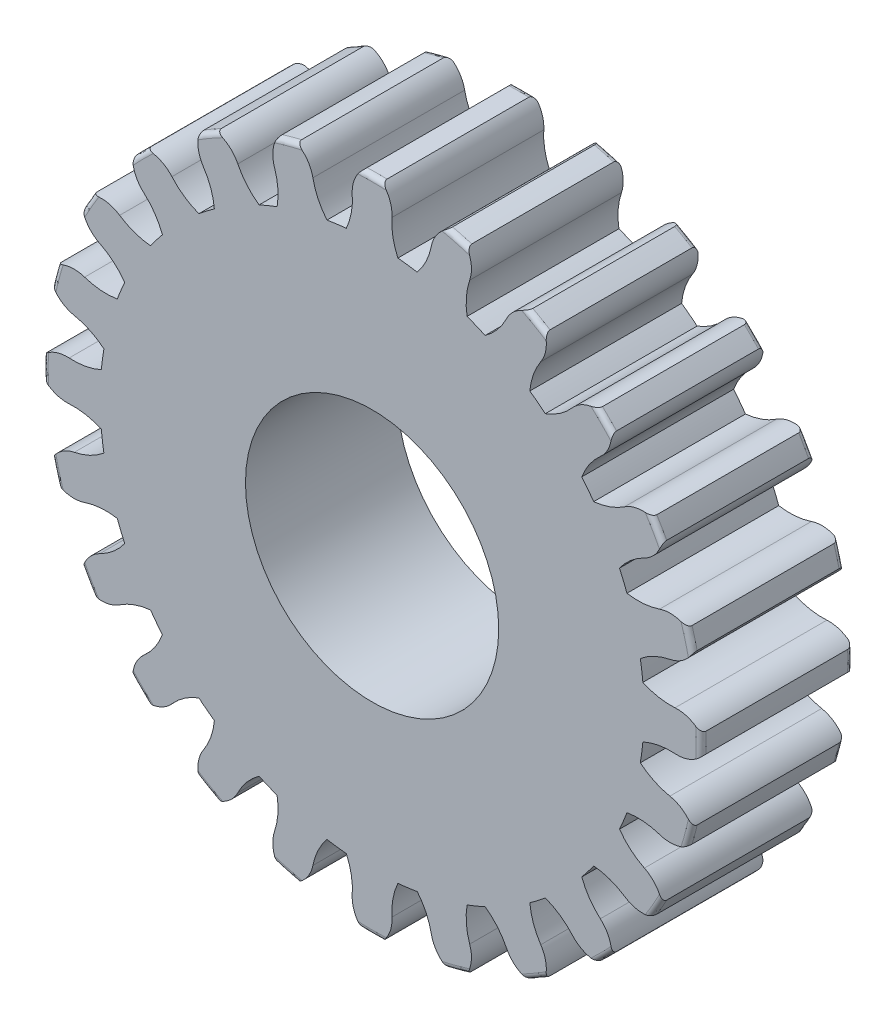
SolidWorks part; units mm, degrees
material "AISI 4130 Steel, annealed at 865C"
ref_plane "Front Plane" through (0, 0, 0) normal (0, 0, 1) x (1, 0, 0)
ref_plane "Top Plane" through (0, 0, 0) normal (0, 1, 0) x (1, 0, 0)
ref_plane "Right Plane" through (0, 0, 0) normal (1, 0, 0) x (0, 0, -1)
sketch "Sketch1" plane through (0, 0, 0) normal (0, 0, 1) x (1, 0, 0)
  circle A0 centre (0, 0) radius 24
  dimension "Pitch circcle" = 48
sketch "Sketch2" plane through (0, 0, 0) normal (0, 0, 1) x (1, 0, 0)
  circle A0 centre (0, 0) radius 21.5
  circle A1 centre (0, 0) radius 26
  circle A2 centre (0, 0) radius 24 construction
  circle A3 centre (0, 0) radius 10.01
  dimension "D1" = 20.02
  dimension "dedendum" = 2.5
  dimension "outercircle" = 2
extrude "Boss-Extrude1" add sketch "Sketch2" along normal mid plane 12 contours A0 A3 region at (-20.8919, 0, 0)
sketch "Sketch3" plane through (0, 0, 0) normal (0, 0, 1) x (1, 0, 0)
  line L0 (0, 0) -> (0, 30.1868) construction
  line L1 (1.5697, 20.5331) -> (1.5697, 28.4748) construction
  line L2 (-1.5697, 23.9486) -> (-6.0739, 92.6704) construction
  line L3 (0, -6.6426) -> (0, 6.6426) construction
  arc A0 (1.5697, 23.9486) -> (-1.5697, 23.9486) centre (0, 0) ccw
  circle A1 centre (0, 0) radius 24 construction
  circle A2 centre (0, 0) radius 21.5 construction
  circle A3 centre (0, 0) radius 26 construction
  arc A4 (-0.7853, 25.9881) -> (0.7853, 25.9881) centre (0, 0) cw
  arc A5 (-2.039, 21.4031) -> (2.039, 21.4031) centre (0, 0) cw
  circle A6 centre (0, 0) radius 21.5 construction
  arc A7 (-2.039, 21.4031) -> (-1.5697, 23.9486) centre (-6.8358, 23.6035) ccw
  arc A8 (-1.5697, 23.9486) -> (-0.7853, 25.9881) centre (1.0308, 24.1191) cw
  arc A9 (2.039, 21.4031) -> (1.5697, 23.9486) centre (6.8358, 23.6035) cw
  arc A10 (1.5697, 23.9486) -> (0.7853, 25.9881) centre (-1.0308, 24.1191) ccw
  point P7 (0, 24)
  dimension "D3" = 0
  dimension "CIrcpitch" = 3.1416
  dimension "D1" = 4.0841
  dimension "D2" = 1.5708
extrude "Boss-Extrude2" add sketch "Sketch3" along normal mid plane 12 contours A8 A7 A5 A9 A10 A4
fillet "Fillet1" radius 0.3927 2 edges at (0, 26, -6) (0, 26, 6)
pattern_circular "CirPattern1" count 24 over 360 about axis through (0, 0, 6) along (0, 0, 1) of "Boss-Extrude2", "Fillet1"
equation "\"Module\"= \"Global Module\"'diameter/nTeeth"
equation "\"nTeeth\"= \"2nTeeth\"'number of teeth"
equation "\"PressureAngle\"= \"GlobalPressureAngle\""
equation "\"GearWidth\"= \"Module\" * 6'Thickness of gear"
equation "\"Pitch_Dia\"= \"Module\" * \"nTeeth\"'effectie diameter of gear"
equation "\"Addendum\"= \"Module\""
equation "\"Dedendumm\"= \"Module\" * 1.25"
equation "\"Base_Dia\"= \"Pitch_Dia\" * cos ( \"PressureAngle\" )"
equation "\"Pitch circcle@Sketch1\"=\"Pitch_Dia\""
equation "\"dedendum@Sketch2\"=\"Dedendumm\""
equation "\"outercircle@Sketch2\"=\"Addendum\""
equation "\"D1@Boss-Extrude1\"=\"GearWidth\""
equation "\"CircPitch\"= ( 3.1415926 * \"Pitch_Dia\" ) / ( \"nTeeth\" * 2 )"
equation "\"CIrcpitch@Sketch3\" = \"CircPitch\""
equation "\"D1@CirPattern1\"=\"nTeeth\""
equation "\"Shaft Dia\"=20"
equation "\"D1@Sketch2\"=\"Shaft Dia\"*\"Shaft Apllicator\"?\""
equation "\"FilletR\"= \"CircPitch\" / ( 2 * 4 )"
equation "\"D1@Boss-Extrude2\"=\"GearWidth\""
equation "\"Has Shaft?\"= 1'0 no /1 yes"
equation "\"Shaft Apllicator\"= \"Has Shaft?\" + 0.001"
equation "\"D1@Sketch3\"=\"CircPitch\"*1.3"
equation "\"D2@Sketch3\"=\"CircPitch\"*0.5"
equation "\"D1@Fillet1\"=\"FilletR\""
equation "\"Global Module\"= 2'Compatibility Number"
equation "\"2nTeeth\"= 24'number of teeth in Gear1"
equation "\"GlobalPressureAngle\"= 10"
